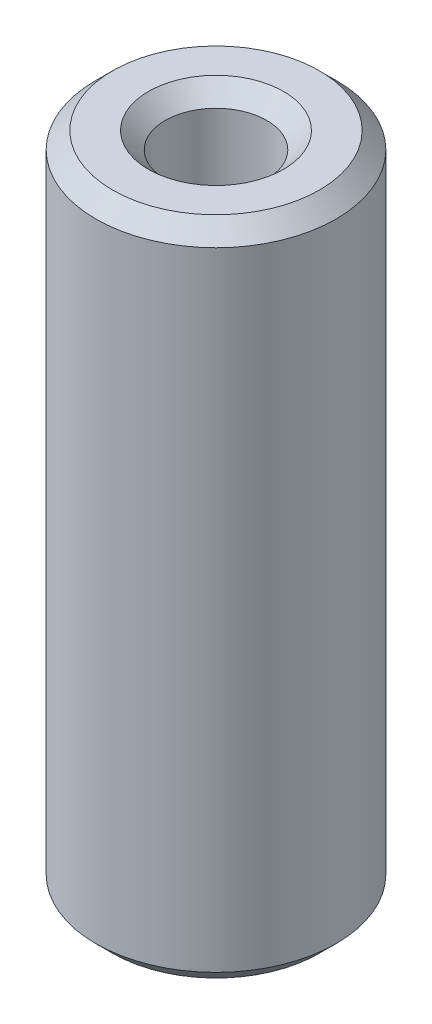
SolidWorks part; units mm, degrees
ref_plane "Front Plane" through (0, 0, 0) normal (0, 0, 1) x (1, 0, 0)
ref_plane "Top Plane" through (0, 0, 0) normal (0, 1, 0) x (1, 0, 0)
ref_plane "Right Plane" through (0, 0, 0) normal (1, 0, 0) x (0, 0, -1)
sketch "Sketch1" plane through (0, 0, 0) normal (0, 1, 0) x (1, 0, 0)
  circle A0 centre (0, 0) radius 27.5
  dimension "SLEEVE_OD" = 55
extrude "Boss-Extrude1" add sketch "Sketch1" along normal blind 151.3492
sketch "Sketch2" plane through (0, 0, 0) normal (0, 1, 0) x (1, 0, 0)
  circle A0 centre (0, 0) radius 11.6313
  dimension "BORE_D" = 23.2627
extrude "Cut-Extrude1" cut sketch "Sketch2" along normal through all
chamfer "Chamfer1" distance 3.8307 angle 45 4 edges at (0, 151.3492, 11.6313) (0, 0, 11.6313) (0, 0, 27.5) (0, 151.3492, 27.5)
